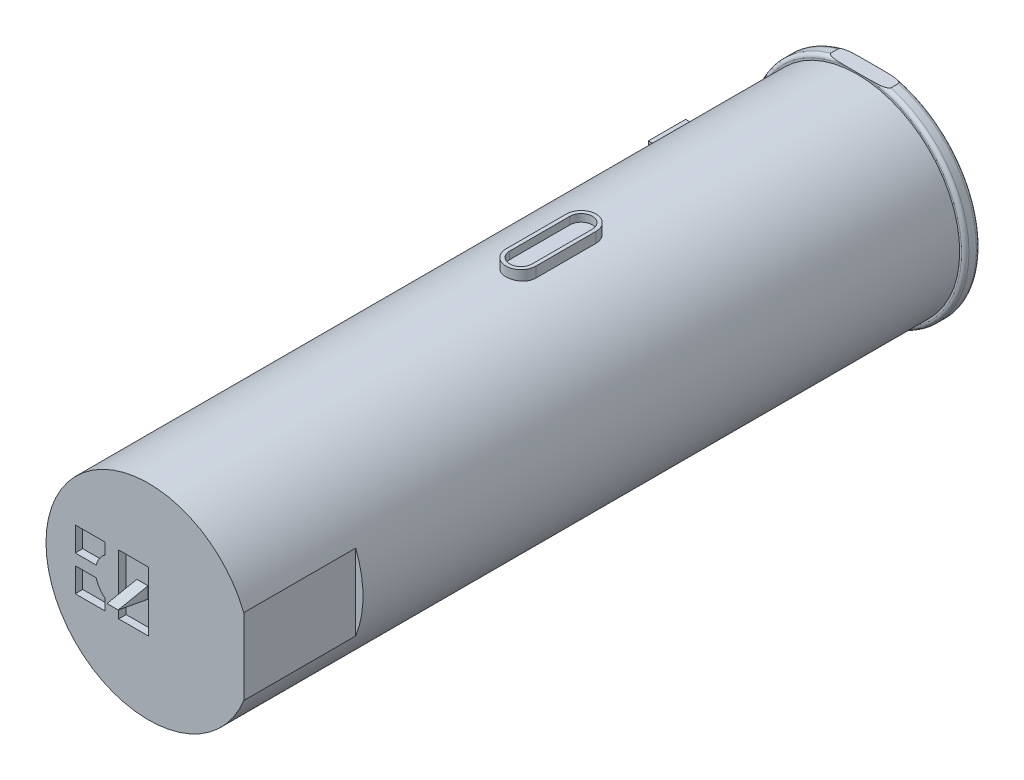
SolidWorks part; units mm, degrees
ref_plane "Front Plane" through (0, 0, 0) normal (0, 0, 1) x (1, 0, 0)
ref_plane "Top Plane" through (0, 0, 0) normal (0, 1, 0) x (1, 0, 0)
ref_plane "Right Plane" through (0, 0, 0) normal (1, 0, 0) x (0, 0, -1)
sketch "Sketch1" plane through (0, 0, 0) normal (0, 0, 1) x (1, 0, 0)
  circle A0 centre (0, 0) radius 13.75
  dimension "D1" = 27.5
extrude "Boss-Extrude1" add sketch "Sketch1" along normal blind 97
sketch "Sketch2" plane through (0, 0, 0) normal (0, 0, -1) x (-1, 0, 0)
  circle A0 centre (0, 0) radius 12
  dimension "D1" = 24
extrude "Cut-Extrude1" cut sketch "Sketch2" against normal blind 78
sketch "Sketch3" plane through (0, 0, 78) normal (0, 0, -1) x (-1, 0, 0)
  line L0 (1.5, -11.9059) -> (1.5, -6.8374)
  line L1 (-1.5, -11.9059) -> (-1.5, -6.8374)
  line L2 (1.5, 6.8374) -> (1.5, 11.9059)
  line L3 (11.9059, 1.5) -> (6.8374, 1.5)
  line L4 (11.9059, -1.5) -> (6.8374, -1.5)
  line L5 (-11.9059, -1.5) -> (-6.8374, -1.5)
  line L6 (-11.9059, 1.5) -> (-6.8374, 1.5)
  line L7 (-1.5, 11.9059) -> (-1.5, 6.8374)
  line L8 (1.5, 11.9059) -> (1.5, 6.8374)
  line L10 (-1.5, 6.8374) -> (-1.5, 11.9059)
  line L12 (-6.8374, 1.5) -> (-11.9059, 1.5)
  line L14 (-6.8374, -1.5) -> (-11.9059, -1.5)
  line L17 (-1.5, -6.8374) -> (-1.5, -11.9059)
  line L19 (1.5, -6.8374) -> (1.5, -11.9059)
  line L21 (6.8374, -1.5) -> (11.9059, -1.5)
  line L23 (6.8374, 1.5) -> (11.9059, 1.5)
  circle A0 centre (0, 0) radius 7
  circle A1 centre (0, 0) radius 12 construction
  circle A2 centre (0, 0) radius 12
  point P27 (0, 0)
  circle M7 centre (0, 0) radius 12
  dimension "D1" = 14
  dimension "D2" = 4
extrude "Cut-Extrude2" cut sketch "Sketch3" against normal blind 15 contours A0 L7 L6 M7 | A0 L3 L2 M7 | A0 L0 L4 M7 | A0 L5 L1 M7 region at (-6.4616, -6.4616, 78) region at (6.4616, -6.4616, 78) region at (6.4616, 6.4616, 78) region at (-6.4616, 6.4616, 78)
sketch "Sketch4" plane through (0, 0, 78) normal (0, 0, -1) x (-1, 0, 0)
  circle A0 centre (0, 0) radius 3
  dimension "D1" = 6
extrude "Cut-Extrude3" cut sketch "Sketch4" against normal blind 15
sketch "Sketch5" plane through (0, 0, 78) normal (0, 0, -1) x (-1, 0, 0)
  circle A0 centre (0, 0) radius 3 construction
  circle A1 centre (0, 0) radius 3
  arc A2 (6.8374, 1.5) -> (1.5, 6.8374) centre (0, 0) ccw construction
  arc A3 (6.8374, 1.5) -> (1.5, 6.8374) centre (0, 0) ccw
  circle A4 centre (0, 0) radius 7
  circle M3 centre (0, 0) radius 3
  arc M6 (-6.8374, -1.5) -> (-1.5, -6.8374) centre (0, 0) ccw
  arc M10 (1.5, -6.8374) -> (6.8374, -1.5) centre (0, 0) ccw
  arc M14 (6.8374, 1.5) -> (1.5, 6.8374) centre (0, 0) ccw
  arc M18 (-1.5, 6.8374) -> (-6.8374, 1.5) centre (0, 0) ccw
extrude "Boss-Extrude2" add sketch "Sketch5" along normal blind 3 contours A4 M14 M18 M6 M10 M3 region at (-6.7624, 0.7331, 78)
sketch "Sketch6" plane through (0, 0, 97) normal (0, 0, 1) x (1, 0, 0)
  line L2 (12.7679, -5.1034) -> (12.7679, 5.1034)
  circle A0 centre (0, 0) radius 13.75 construction
  circle A1 centre (0, 0) radius 13.75
  circle M3 centre (0, 0) radius 13.75
extrude "Cut-Extrude4" cut sketch "Sketch6" against normal blind 15 contours L2 M3 region at (13.1619, 0, 97)
sketch "Sketch7" plane through (0, 0, 97) normal (0, 0, 1) x (1, 0, 0)
  line L1 (0, -4) -> (0, 4)
  line L2 (0, 4) -> (-4, 4)
  line L3 (-4, 4) -> (-4, -4)
  line L4 (0, -4) -> (-4, -4)
  line L5 (-9.8281, -4) -> (-9.8281, -0.7409)
  line L6 (-9.8281, 4) -> (-5.8281, 4)
  line L7 (-5.8281, 2.5025) -> (-5.8281, 4)
  line L8 (-9.8281, -4) -> (-5.8281, -4)
  line L9 (-5.8281, -2.5025) -> (-5.8281, -4)
  line L10 (-9.8281, 0.7409) -> (-9.8281, 4)
  line L12 (-9.8281, 0.7409) -> (-7.0093, 0.7409)
  line L13 (-9.8281, -0.7409) -> (-7.0093, -0.7409)
  arc A1 (-5.8281, 2.5025) -> (-7.0093, 0.7409) centre (-4, 0) ccw
  arc A2 (-7.0093, -0.7409) -> (-5.8281, -2.5025) centre (-4, 0) ccw
  point P12 (-4, 0)
  point P19 (-9.8281, 0)
  dimension "D1" = 4
  dimension "D2" = 4
  dimension "D3" = 4
extrude "Cut-Extrude5" cut sketch "Sketch7" against normal blind 4
ref_plane "Plane1" through (0, 0, 96) normal (0, 0, 1) x (1, 0, 0)
sketch "Sketch8" plane through (0, 0, 96) normal (0, 0, 1) x (1, 0, 0)
  line L0 (0, -4) -> (0, 4) construction
  line L1 (12.7679, -5.1034) -> (12.7679, 5.1034)
  line L2 (12.7679, -5.1034) -> (12.7679, 5.1034)
  line L3 (-9.8281, 4) -> (-9.8281, 0.7409) construction
  line L4 (-9.8281, -0.7409) -> (-9.8281, -4) construction
  line L5 (0, -4) -> (0, 4)
  line L6 (-9.8281, 4) -> (-9.8281, 0.7409)
  line L7 (-9.8281, -0.7409) -> (-9.8281, -4)
  line L8 (-9.8281, -4) -> (0, -4)
  line L9 (0, 4) -> (-9.8281, 4)
  line L10 (-9.8281, -0.7409) -> (-9.8281, 0.7409)
  arc A1 (12.7679, 5.1034) -> (12.7679, -5.1034) centre (0, 0) ccw
  arc A2 (12.7679, 5.1034) -> (12.7679, -5.1034) centre (0, 0) ccw
  dimension "D1" = 0
extrude "Boss-Extrude3" add sketch "Sketch8" against normal blind 1 contours L10 L6 L9 L5 L8 L7
sketch "Sketch9" plane through (0, 0, 96) normal (0, 0, 1) x (1, 0, 0)
  line L0 (-1.0655, -1.9111) -> (-1.0655, 1.8331)
  line L1 (-1.0655, -1.9111) -> (-1.7286, -1.9111)
  line L2 (-1.7286, -1.9111) -> (-1.7286, 1.8331)
  line L3 (-1.7286, 1.8331) -> (-1.0655, 1.8331)
ref_plane "Plane2" through (-1.0655, 0, 0) normal (1, 0, 0) x (0, 1, 0)
sketch "Sketch10" plane through (-1.0655, 0, 0) normal (1, 0, 0) x (0, 1, 0)
  line L0 (-1.9111, 96) -> (1.8331, 96) construction
  line L1 (-0.7516, 96) -> (0.811, 96)
  line L2 (0.811, 96) -> (0, 100)
  line L3 (0, 100) -> (-0.7516, 96)
  dimension "D1" = 4
extrude "Boss-Extrude4" add sketch "Sketch10" against normal blind 1.5
sketch "Sketch11" plane through (0, 0, 0) normal (0, 0, -1) x (-1, 0, 0)
  circle A0 centre (0, 0) radius 12 construction
  circle A1 centre (0, 0) radius 12
  circle A2 centre (0, 0) radius 13.75 construction
  circle A3 centre (0, 0) radius 13.75
  circle A4 centre (0, 0) radius 14.5
  circle M2 centre (0, 0) radius 13.75
extrude "Boss-Extrude5" add sketch "Sketch11" against normal blind 2 contours A4 M2 region at (14.0899, 0, 0)
fillet "Fillet1" radius 0.5 3 edges at (-14.5, 0, 0) (-12, 0, 0) (-14.5, 0, 2)
sketch "Sketch12" plane through (0, 0, 0) normal (0, 1, 0) x (1, 0, 0)
  line L0 (1.1278, -97) -> (1.1278, -48.7315) construction
  line L1 (-13.75, -97) -> (12.7679, -97) construction
  line L2 (0, -49.7147) -> (0, -33.7736) construction
  line L3 (0, -15.125) -> (0, 15.125) construction
  line L4 (-2, -47.0798) -> (-2, -39)
  line L5 (2, -47.0798) -> (2, -39)
  arc A0 (2, -39) -> (-2, -39) centre (0, -39) ccw
  arc A1 (-2, -47.0798) -> (2, -47.0798) centre (0, -47.0798) ccw
extrude "Boss-Extrude6" add sketch "Sketch12" along normal blind 15
sketch "Sketch13" plane through (0, 15, 0) normal (0, 1, 0) x (1, 0, 0)
  line L0 (-1.5, -47.0798) -> (-1.5, -39)
  line L2 (1.5, -39) -> (1.4993, -47.0343)
  arc A0 (2, -39) -> (-2, -39) centre (0, -39) ccw construction
  arc A1 (-2, -47.0798) -> (2, -47.0798) centre (0, -47.0798) ccw construction
  arc A2 (2, -39) -> (-2, -39) centre (0, -39) ccw
  arc A3 (-2, -47.0798) -> (2, -47.0798) centre (0, -47.0798) ccw
  arc A4 (-1.5, -47.0798) -> (1.4993, -47.0343) centre (0, -47.0798) ccw
  arc A5 (1.5, -39) -> (-1.5, -39) centre (0, -39) ccw
  dimension "D1" = 3
  dimension "D2" = 3
extrude "Cut-Extrude6" cut sketch "Sketch13" against normal blind 1 contours L2 A5 L0 A4 region at (-0.0001, 15, 43.0398)
sketch "Sketch16" plane through (0, 0, 0) normal (0, -1, 0) x (1, 0, 0)
  line L2 (-2, 47.0798) -> (-2, 39)
  line L3 (2, 39) -> (2, 47.0798)
  line L4 (-2, 47.0798) -> (-2, 39)
  line L5 (2, 39) -> (2, 47.0798)
  arc A2 (2, 47.0798) -> (-2, 47.0798) centre (0, 47.0798) ccw
  arc A3 (-2, 39) -> (2, 39) centre (0, 39) ccw
  arc A4 (2, 47.0798) -> (-2, 47.0798) centre (0, 47.0798) ccw
  arc A5 (-2, 39) -> (2, 39) centre (0, 39) ccw
  dimension "D1" = 0
extrude "Cut-Extrude7" cut sketch "Sketch16" against normal up to surface (11.8322 mm away) contours A4 L4 A5 L5 up to face at (0, 0, 85.5)
sketch "Sketch17" plane through (0, 0, 0) normal (1, 0, 0) x (0, 0, -1)
  line L0 (0, -14) -> (0, 14) construction
  line L1 (0, -14) -> (0, 14)
  line L2 (-5, 0) -> (-5, -1.7442)
  line L3 (-5, 0) -> (-10, 0)
  line L4 (-5, -1.7442) -> (-8.6498, -1.7442)
  line L5 (-10, -1.7442) -> (-10, 0)
  line L6 (-10, -1.7442) -> (-10, -3.5448)
  line L7 (-10, -3.5448) -> (-8.6498, -3.5448)
  line L8 (-8.6498, -3.5448) -> (-8.6498, -1.7442)
  dimension "D2" = 5
extrude "Boss-Extrude7" add sketch "Sketch17" against normal blind 20 contours L3 L5 L6 L7 L8 L4 L2
sketch "Sketch18" plane through (0, 0, 0) normal (1, 0, 0) x (0, 0, -1)
  line L6 (-5, -1.7442) -> (-5, 0)
  line L7 (-5, 0) -> (-10, 0)
  line L8 (-10, 0) -> (-10, -3.5448)
  line L9 (-10, -3.5448) -> (-8.6498, -3.5448)
  line L10 (-8.6498, -3.5448) -> (-8.6498, -1.7442)
  line L11 (-8.6498, -1.7442) -> (-5, -1.7442)
  line L12 (-5, -1.7442) -> (-5, 0)
  line L13 (-5, 0) -> (-10, 0)
  line L14 (-10, 0) -> (-10, -3.5448)
  line L15 (-10, -3.5448) -> (-8.6498, -3.5448)
  line L16 (-8.6498, -3.5448) -> (-8.6498, -1.7442)
  line L17 (-8.6498, -1.7442) -> (-5, -1.7442)
  dimension "D1" = 0
extrude "Cut-Extrude8" cut sketch "Sketch18" against normal up to surface (11.4645 mm away) up to face at (12, 0, 0.5)
sketch "Sketch19" plane through (0, 0, 10) normal (0, 0, 1) x (1, 0, 0)
  circle A0 centre (-17.5751, -1.7586) radius 1.0717
extrude "Boss-Extrude8" add sketch "Sketch19" along normal blind 3
sketch "Sketch20" plane through (0, 0, 0) normal (0, 0, -1) x (-1, 0, 0)
  line L0 (-4.0347, -13.9274) -> (4.0347, -13.9274)
  line L1 (18.975, 0) -> (-18.975, 0) construction
  line L2 (-4.0347, 13.9274) -> (4.0347, 13.9274)
  circle A3 centre (0, 0) radius 14.5 construction
  circle A4 centre (0, 0) radius 14.5
  circle A5 centre (0, 0) radius 14 construction
  arc A6 (-1.4242, 13.9274) -> (-1.4242, -13.9274) centre (0, 0) ccw
  arc A7 (1.4242, -13.9274) -> (1.4242, 13.9274) centre (0, 0) ccw
  point P15 (0, 0)
  point P16 (0, 0)
  circle M3 centre (0, 0) radius 14
extrude "Cut-Extrude9" cut sketch "Sketch20" against normal blind 3 contours L0 A4 M3 | L0 M3 region at (0, -14.1662, 0) region at (0, -13.9564, 0)
mirror "Mirror1" about plane through (0, 0, 0) normal (0, 1, 0) of "Cut-Extrude9"
